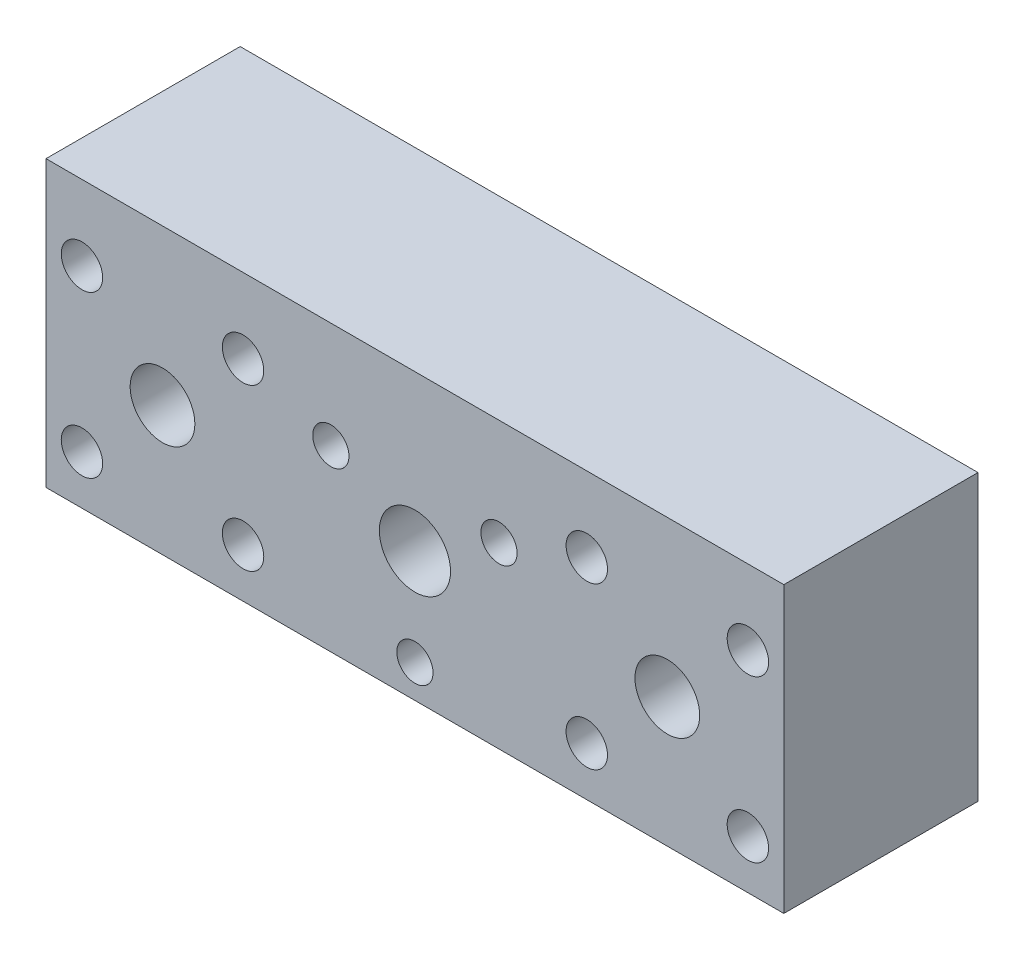
SolidWorks part; units mm, degrees
ref_plane "Front Plane" through (0, 0, 0) normal (0, 0, 1) x (1, 0, 0)
ref_plane "Top Plane" through (0, 0, 0) normal (0, 1, 0) x (1, 0, 0)
ref_plane "Right Plane" through (0, 0, 0) normal (1, 0, 0) x (0, 0, -1)
sketch "Sketch1" plane through (0, 0, 0) normal (0, 0, 1) x (1, 0, 0)
  line L0 (0, 33.8286) -> (0, -41.7271) construction
  line L1 (-36.195, 11.43) -> (36.195, 11.43)
  line L2 (-36.195, 11.43) -> (-36.195, -11.43)
  line L3 (-36.195, -11.43) -> (36.195, -11.43)
  line L4 (36.195, 11.43) -> (36.195, -11.43)
  circle A0 centre (-24.765, 0) radius 3.175
  circle A1 centre (24.765, 0) radius 3.175
  circle A2 centre (0, 0) radius 3.4925
  point P4 (-36.195, 0)
  point P6 (0, 11.43)
  dimension "D3" = 6.985
  dimension "D5" = 6.35
  dimension "D1" = 72.39
  dimension "D2" = 22.86
  dimension "D4" = 49.53
extrude "Boss-Extrude1" add sketch "Sketch1" along normal blind 6.35 contours L1 L4 L3 L2
extrude "Cut-Extrude3" cut sketch "Sketch1<3>" along normal blind 12.7 contours L0 A2 | A2 L0 | A1 | A0 region at (1.4823, 0, 0) region at (-1.4823, 0, 0) region at (-24.765, 0, 0) region at (24.765, 0, 0)
sketch "Sketch1<3>" plane through (0, 0, 0) normal (0, 0, 1) x (1, 0, 0) same geometry as "Sketch1"
sketch "Sketch2" plane through (0, 0, 6.35) normal (0, 0, 1) x (1, 0, 0)
  line L0 (24.765, -3.175) -> (24.765, 3.175) construction
  line L1 (27.94, 0) -> (21.59, 0) construction
  line L2 (24.765, 0) -> (36.195, -11.43) construction
  line L3 (0, -15.0371) -> (0, 15.9916) construction
  line L5 (36.195, 11.43) -> (36.195, -11.43) construction
  circle A9 centre (24.765, 0) radius 3.175 construction
  circle A10 centre (32.6676, -7.9026) radius 2.032
  circle A11 centre (32.6676, 7.9026) radius 2.032
  circle A12 centre (16.8624, 7.9026) radius 2.032
  circle A13 centre (16.8624, -7.9026) radius 2.032
  circle A14 centre (-16.8624, 7.9026) radius 2.032
  circle A15 centre (-32.6676, 7.9026) radius 2.032
  circle A16 centre (-16.8624, -7.9026) radius 2.032
  circle A17 centre (-32.6676, -7.9026) radius 2.032
  dimension "D3" = 4.064
  dimension "D1" = 45
  dimension "D2" = 11.176
extrude "Cut-Extrude4" cut sketch "Sketch2" against normal through all
sketch "Sketch3" plane through (0, 0, 6.35) normal (0, 0, 1) x (1, 0, 0)
  line L0 (0, 0) -> (28.7826, 0) construction
  line L1 (8.2486, 4.826) -> (-8.2487, 4.826) construction
  line L2 (-36.195, 11.43) -> (36.195, 11.43) construction
  line L3 (0, -7.6831) -> (0, -9.4611) construction
  circle A0 centre (8.2486, 4.826) radius 1.778
  circle A1 centre (-8.2487, 4.826) radius 1.778
  circle A2 centre (0, -9.4611) radius 1.778
  dimension "D4" = 3.556
  dimension "D1" = 16.4973
  dimension "D2" = 16.4973
  dimension "D3" = 16.4973
  dimension "D5" = 6.604
extrude "Cut-Extrude5" cut sketch "Sketch3" against normal through all
sketch "Sketch4" plane through (0, -11.43, 0) normal (0, -1, 0) x (1, 0, 0)
  line L4 (-36.195, 0) -> (36.195, 0)
  line L5 (36.195, 0) -> (36.195, 6.35)
  line L6 (36.195, 6.35) -> (-36.195, 6.35)
  line L7 (-36.195, 6.35) -> (-36.195, 0)
  line L8 (-36.195, 0) -> (36.195, 0)
  line L9 (36.195, 0) -> (36.195, 6.35)
  line L10 (36.195, 6.35) -> (-36.195, 6.35)
  line L11 (-36.195, 6.35) -> (-36.195, 0)
  dimension "D1" = 0
extrude "Boss-Extrude2" add sketch "Sketch4" along normal blind 1.27
sketch "Sketch5" plane through (0, 11.43, 0) normal (0, 1, 0) x (1, 0, 0)
  line L4 (36.195, 0) -> (-36.195, 0)
  line L5 (-36.195, 0) -> (-36.195, -6.35)
  line L6 (-36.195, -6.35) -> (36.195, -6.35)
  line L7 (36.195, -6.35) -> (36.195, 0)
  line L8 (36.195, 0) -> (-36.195, 0)
  line L9 (-36.195, 0) -> (-36.195, -6.35)
  line L10 (-36.195, -6.35) -> (36.195, -6.35)
  line L11 (36.195, -6.35) -> (36.195, 0)
  dimension "D1" = 0
extrude "Boss-Extrude3" add sketch "Sketch5" along normal blind 3.81
sketch "Sketch7" plane through (0, 0, 0) normal (0, 0, -1) x (-1, 0, 0)
  line L0 (-36.195, 15.24) -> (-36.195, -12.7) construction
  line L1 (-36.195, 15.24) -> (36.195, 15.24) construction
  line L2 (36.195, 15.24) -> (36.195, -12.7) construction
  line L3 (36.195, -12.7) -> (-36.195, -12.7) construction
  line L4 (-36.195, 15.24) -> (-36.195, -12.7)
  line L5 (-36.195, 15.24) -> (36.195, 15.24)
  line L6 (36.195, 15.24) -> (36.195, -12.7)
  line L7 (36.195, -12.7) -> (-36.195, -12.7)
  circle A0 centre (-24.765, 0) radius 3.175 construction
  circle A1 centre (0, 0) radius 3.4925 construction
  circle A2 centre (24.765, 0) radius 3.175 construction
  circle A3 centre (-24.765, 0) radius 3.175
  circle A4 centre (0, 0) radius 3.4925
  circle A5 centre (24.765, 0) radius 3.175
extrude "Boss-Extrude4" add sketch "Sketch7" along normal blind 12.7
